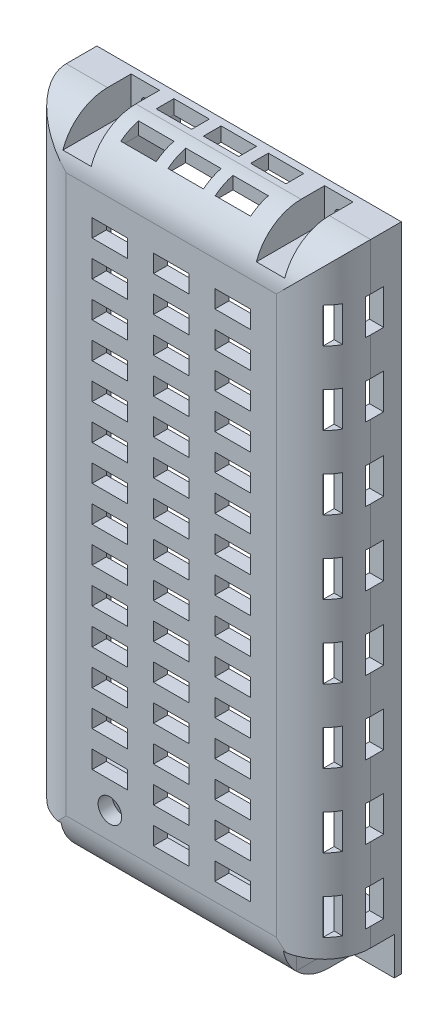
SolidWorks part; units mm, degrees
ref_plane "Plano frontal" through (0, 0, 0) normal (0, 0, 1) x (1, 0, 0)
ref_plane "Plano superior" through (0, 0, 0) normal (0, 1, 0) x (1, 0, 0)
ref_plane "Plano direito" through (0, 0, 0) normal (1, 0, 0) x (0, 0, -1)
sketch "Esboço1" plane through (0, 0, 0) normal (0, 0, 1) x (1, 0, 0)
  line L0 (-47.125, -132) -> (-47.125, -122)
  line L1 (-64.5, 138) -> (64.5, 138)
  line L2 (-64.5, 138) -> (-64.5, -138)
  line L3 (-64.5, -138) -> (64.5, -138)
  line L4 (64.5, 138) -> (64.5, -138)
  line L5 (0, -138) -> (0, 138) construction
  line L6 (-64.5, 0) -> (64.5, 0) construction
  line L7 (-58.5, 132) -> (58.5, 132) construction
  line L8 (-58.5, 132) -> (-58.5, -132) construction
  line L9 (-58.5, -132) -> (58.5, -132) construction
  line L10 (58.5, 132) -> (58.5, -132) construction
  line L11 (0, -132) -> (0, 132) construction
  line L12 (-58.5, 0) -> (58.5, 0) construction
  line L13 (-47.125, -122) -> (-58.5, -122)
  line L14 (-47, 132) -> (-47, 124.5)
  line L15 (-47, 124.5) -> (-35, 124.5)
  line L16 (-35, 124.5) -> (-35, 132)
  line L17 (-41, 130.5) -> (-41, 124.5) construction
  line L18 (-41, 130.5) -> (-35, 130.5) construction
  line L19 (-47, 132) -> (-58.5, 132)
  line L20 (-58.5, 132) -> (-58.5, -122)
  line L21 (41, 130.5) -> (35, 130.5) construction
  line L22 (41, 130.5) -> (41, 124.5) construction
  line L23 (47, 132) -> (58.5, 132)
  line L24 (35, 124.5) -> (35, 132)
  line L25 (47, 124.5) -> (35, 124.5)
  line L26 (47, 132) -> (47, 124.5)
  line L27 (58.5, 132) -> (58.5, -132) construction
  line L28 (58.5, 132) -> (58.5, -122)
  line L29 (47.125, -122) -> (58.5, -122)
  line L30 (47.125, -132) -> (47.125, -122)
  line L31 (-35, 132) -> (35, 132)
  line L32 (47.125, -132) -> (-47.125, -132)
  circle A0 centre (-53.125, -128) radius 1.6
  circle A1 centre (-41, 130.5) radius 1.6
  circle A2 centre (41, 130.5) radius 1.6
  circle A3 centre (53.125, -128) radius 1.6
  point P56 (0, 0)
  point P83 (0, 0)
  dimension "D5" = 3.2
  dimension "D8" = 3.2
  dimension "D1" = 129
  dimension "D2" = 276
  dimension "D3" = 6
  dimension "D4" = 6
  dimension "D6" = 11.375
  dimension "D7" = 10
  dimension "D9" = 23.5
  dimension "D10" = 7.5
  dimension "D11" = 6
  dimension "D12" = 6
  dimension "D13" = 6
extrude "Ressalto-extrusão1" add sketch "Esboço1" along normal blind 3
sketch "Esboço4" plane through (0, 0, 3) normal (0, 0, 1) x (1, 0, 0)
  line L0 (-64.5, 138) -> (-64.5, 72)
  line L1 (-64.5, 138) -> (-64.5, -138) construction
  line L2 (-64.5, 72) -> (-58.5, 72)
  line L3 (-58.5, 132) -> (-58.5, -122) construction
  line L4 (-58.5, 72) -> (-58.5, 132)
  line L5 (-58.5, 132) -> (-47, 132)
  line L6 (-47, 132) -> (-47, 138)
  line L7 (64.5, 138) -> (-64.5, 138) construction
  line L8 (-47, 138) -> (-64.5, 138)
  line L9 (-35, 132) -> (-35, 138)
  line L10 (-35, 138) -> (35, 138)
  line L11 (35, 138) -> (35, 132)
  line L12 (35, 132) -> (-35, 132)
  line L13 (47, 132) -> (47, 138)
  line L14 (47, 138) -> (64.5, 138)
  line L15 (64.5, 138) -> (64.5, 72)
  line L16 (64.5, -138) -> (64.5, 138) construction
  line L17 (64.5, 72) -> (58.5, 72)
  line L18 (58.5, -122) -> (58.5, 132) construction
  line L19 (58.5, 72) -> (58.5, 132)
  line L20 (58.5, 132) -> (47, 132)
  line L21 (-47.125, -132) -> (-47.125, -138)
  line L22 (-64.5, -138) -> (64.5, -138) construction
  line L23 (-47.125, -138) -> (47, -138)
  line L24 (47, -138) -> (47.125, -132)
  line L25 (47.125, -132) -> (-47.125, -132)
  line L26 (-58.5, -122) -> (-64.5, -122)
  line L27 (-64.5, -122) -> (-64.5, -22)
  line L28 (-64.5, -22) -> (-58.5, -22)
  line L29 (-58.5, -22) -> (-58.5, -122)
  line L30 (58.5, -122) -> (64.5, -122)
  line L31 (64.5, -122) -> (64.5, -22)
  line L32 (64.5, -22) -> (58.5, -22)
  line L33 (58.5, -22) -> (58.5, -122)
  dimension "D1" = 60
  dimension "D2" = 100
extrude "Ressalto-extrusão2" add sketch "Esboço4" along normal blind 24
sketch "Esboço5" plane through (0, 0, 27) normal (0, 0, 1) x (1, 0, 0)
  line L0 (-35, 132) -> (-35, 138)
  line L1 (-35, 138) -> (35, 138)
  line L2 (35, 138) -> (35, 132)
  line L3 (47, 132) -> (47, 138)
  line L4 (47, 138) -> (64.5, 138)
  line L5 (64.5, 138) -> (64.5, 72)
  line L6 (64.5, 72) -> (58.5, 72)
  line L7 (58.5, 72) -> (-64.5, 72)
  line L8 (-64.5, 72) -> (-64.5, 138)
  line L9 (-64.5, 138) -> (-47, 138)
  line L10 (-47, 138) -> (-47, 124.5)
  line L11 (-47, 124.5) -> (-35, 124.5)
  line L12 (-35, 124.5) -> (-35, 132)
  line L13 (35, 132) -> (35, 124.5)
  line L14 (35, 124.5) -> (47, 124.5)
  line L15 (47, 124.5) -> (47, 132)
  line L16 (-47.125, -138) -> (47, -138)
  line L17 (47, -138) -> (47.125, -122)
  line L18 (47.125, -122) -> (64.5, -122)
  line L19 (64.5, -122) -> (64.5, -22)
  line L20 (64.5, -22) -> (-64.5, -22)
  line L21 (-64.5, -22) -> (-64.5, -122)
  line L22 (-64.5, -122) -> (-47.125, -122)
  line L23 (-47.125, -122) -> (-47.125, -138)
extrude "Ressalto-extrusão3" add sketch "Esboço5" along normal blind 6
sketch "Esboço7" plane through (0, 0, 27) normal (0, 0, -1) x (-1, 0, 0)
  line L0 (-47, 132) -> (-53, 132)
  line L1 (-47, 132) -> (-58.5, 132) construction
  line L2 (-53, 132) -> (-53, 118.5)
  line L3 (-53, 118.5) -> (-29, 118.5)
  line L4 (-29, 118.5) -> (-29, 132)
  line L5 (35, 132) -> (-35, 132) construction
  line L6 (-29, 132) -> (-35, 132)
  line L7 (-35, 132) -> (-35, 124.5)
  line L8 (-35, 124.5) -> (-47, 124.5)
  line L9 (-47, 132) -> (-47, 124.5) construction
  line L10 (-47, 124.5) -> (-35, 124.5) construction
  line L11 (-47, 124.5) -> (-47, 132)
  line L19 (0, 0) -> (0, 50000) construction
  line L20 (58.5, -122) -> (58.5, -22) construction
  line L27 (47.125, -132) -> (47.125, -122)
  line L28 (47.125, -122) -> (58.5, -122)
  line L29 (58.5, -122) -> (58.5, -116)
  line L30 (58.5, -116) -> (41.125, -116)
  line L31 (41.125, -116) -> (41.125, -132)
  line L32 (-47.0469, -132) -> (47.125, -132) construction
  line L33 (41.125, -132) -> (47.125, -132)
  line L34 (47, 124.5) -> (47, 132)
  line L35 (35, 124.5) -> (47, 124.5)
  line L36 (35, 132) -> (35, 124.5)
  line L37 (29, 132) -> (35, 132)
  line L38 (29, 118.5) -> (29, 132)
  line L39 (53, 118.5) -> (29, 118.5)
  line L40 (53, 132) -> (53, 118.5)
  line L41 (47, 132) -> (53, 132)
  line L42 (-41.125, -132) -> (-47.125, -132)
  line L43 (-41.125, -116) -> (-41.125, -132)
  line L44 (-58.5, -116) -> (-41.125, -116)
  line L45 (-58.5, -122) -> (-58.5, -116)
  line L46 (-47.125, -122) -> (-58.5, -122)
  line L47 (-47.125, -132) -> (-47.125, -122)
  dimension "D1" = 6
  dimension "D2" = 6
  dimension "D5" = 6
extrude "Ressalto-extrusão5" add sketch "Esboço7" along normal up to vertex (27 mm away) up to point (35, 124.5, 0)
sketch "Esboço8" plane through (0, -22, 0) normal (0, 1, 0) x (1, 0, 0)
  line L0 (-58.5, -3) -> (-64.5, -3)
  line L1 (-64.5, -3) -> (-64.5, -33)
  line L2 (-64.5, -33) -> (64.5, -33)
  line L3 (64.5, -33) -> (64.5, -3)
  line L4 (64.5, -3) -> (58.5, -3)
  line L5 (58.5, -3) -> (58.5, -27)
  line L6 (58.5, -27) -> (-58.5, -27)
  line L7 (-58.5, -27) -> (-58.5, -3)
extrude "Ressalto-extrusão6" add sketch "Esboço8" along normal up to vertex (94 mm away) up to point (-58.5, 72, 27)
fillet "Filete1" radius 20 4 edges at (0, 138, 33) (-0.0625, -138, 33) (64.5, 8, 33) (-64.5, 8, 33)
sketch "Esboço9" plane through (0, 0, 33) normal (0, 0, 1) x (1, 0, 0)
  line L2 (-18.5, -106.75) -> (-7.5, -106.75) construction
  line L7 (-33.5, -103) -> (-18.5, -103) construction
  line L8 (-33.5, -103) -> (-33.5, -110.5) construction
  line L9 (-33.5, -110.5) -> (-18.5, -110.5) construction
  line L10 (-18.5, -103) -> (-18.5, -110.5) construction
  line L11 (-26, -110.5) -> (-26, -103) construction
  line L12 (-33.5, -106.75) -> (-18.5, -106.75) construction
  line L13 (-7.5, -103) -> (7.5, -103)
  line L14 (-7.5, -103) -> (-7.5, -110.5)
  line L15 (-7.5, -110.5) -> (7.5, -110.5)
  line L16 (7.5, -103) -> (7.5, -110.5)
  line L17 (0, -110.5) -> (0, -103) construction
  line L18 (-7.5, -106.75) -> (7.5, -106.75) construction
  line L19 (18.5, -103) -> (33.5, -103)
  line L20 (18.5, -103) -> (18.5, -110.5)
  line L21 (18.5, -110.5) -> (33.5, -110.5)
  line L22 (33.5, -103) -> (33.5, -110.5)
  line L23 (26, -110.5) -> (26, -103) construction
  line L24 (18.5, -106.75) -> (33.5, -106.75) construction
  line L25 (7.5, -106.75) -> (18.5, -106.75) construction
  line L26 (-33.5, -106.75) -> (-44.5, -106.75) construction
  line L27 (-44.5, 118) -> (-44.5, -118) construction
  line L28 (33.5, -106.75) -> (44.5, -106.75) construction
  line L29 (44.5, -118) -> (44.5, 118) construction
  line L30 (-44.5, -118) -> (44.5, -118) construction
  line L31 (-33.5, -88) -> (-18.5, -88)
  line L32 (-33.5, -88) -> (-33.5, -95.5)
  line L33 (-33.5, -95.5) -> (-18.5, -95.5)
  line L34 (-18.5, -88) -> (-18.5, -95.5)
  line L35 (-7.5, -88) -> (7.5, -88)
  line L36 (-7.5, -88) -> (-7.5, -95.5)
  line L37 (-7.5, -95.5) -> (7.5, -95.5)
  line L38 (7.5, -88) -> (7.5, -95.5)
  line L39 (18.5, -88) -> (33.5, -88)
  line L40 (18.5, -88) -> (18.5, -95.5)
  line L41 (18.5, -95.5) -> (33.5, -95.5)
  line L42 (33.5, -88) -> (33.5, -95.5)
  line L43 (-18.5, -91.75) -> (-7.5, -91.75) construction
  line L44 (-26, -95.5) -> (-26, -88) construction
  line L45 (-33.5, -91.75) -> (-18.5, -91.75) construction
  line L46 (0, -95.5) -> (0, -88) construction
  line L47 (-7.5, -91.75) -> (7.5, -91.75) construction
  line L48 (26, -95.5) -> (26, -88) construction
  line L49 (18.5, -91.75) -> (33.5, -91.75) construction
  line L50 (7.5, -91.75) -> (18.5, -91.75) construction
  line L51 (-33.5, -73) -> (-18.5, -73)
  line L52 (-33.5, -73) -> (-33.5, -80.5)
  line L53 (-33.5, -80.5) -> (-18.5, -80.5)
  line L54 (-18.5, -73) -> (-18.5, -80.5)
  line L55 (-7.5, -73) -> (7.5, -73)
  line L56 (-7.5, -73) -> (-7.5, -80.5)
  line L57 (-7.5, -80.5) -> (7.5, -80.5)
  line L58 (7.5, -73) -> (7.5, -80.5)
  line L59 (18.5, -73) -> (33.5, -73)
  line L60 (18.5, -73) -> (18.5, -80.5)
  line L61 (18.5, -80.5) -> (33.5, -80.5)
  line L62 (33.5, -73) -> (33.5, -80.5)
  line L63 (-18.5, -76.75) -> (-7.5, -76.75) construction
  line L64 (-26, -80.5) -> (-26, -73) construction
  line L65 (-33.5, -76.75) -> (-18.5, -76.75) construction
  line L66 (0, -80.5) -> (0, -73) construction
  line L67 (-7.5, -76.75) -> (7.5, -76.75) construction
  line L68 (26, -80.5) -> (26, -73) construction
  line L69 (18.5, -76.75) -> (33.5, -76.75) construction
  line L70 (7.5, -76.75) -> (18.5, -76.75) construction
  line L71 (-33.5, -58) -> (-18.5, -58)
  line L72 (-33.5, -58) -> (-33.5, -65.5)
  line L73 (-33.5, -65.5) -> (-18.5, -65.5)
  line L74 (-18.5, -58) -> (-18.5, -65.5)
  line L75 (-7.5, -58) -> (7.5, -58)
  line L76 (-7.5, -58) -> (-7.5, -65.5)
  line L77 (-7.5, -65.5) -> (7.5, -65.5)
  line L78 (7.5, -58) -> (7.5, -65.5)
  line L79 (18.5, -58) -> (33.5, -58)
  line L80 (18.5, -58) -> (18.5, -65.5)
  line L81 (18.5, -65.5) -> (33.5, -65.5)
  line L82 (33.5, -58) -> (33.5, -65.5)
  line L83 (-18.5, -61.75) -> (-7.5, -61.75) construction
  line L84 (-26, -65.5) -> (-26, -58) construction
  line L85 (-33.5, -61.75) -> (-18.5, -61.75) construction
  line L86 (0, -65.5) -> (0, -58) construction
  line L87 (-7.5, -61.75) -> (7.5, -61.75) construction
  line L88 (26, -65.5) -> (26, -58) construction
  line L89 (18.5, -61.75) -> (33.5, -61.75) construction
  line L90 (7.5, -61.75) -> (18.5, -61.75) construction
  line L91 (-33.5, -43) -> (-18.5, -43)
  line L92 (-33.5, -43) -> (-33.5, -50.5)
  line L93 (-33.5, -50.5) -> (-18.5, -50.5)
  line L94 (-18.5, -43) -> (-18.5, -50.5)
  line L95 (-7.5, -43) -> (7.5, -43)
  line L96 (-7.5, -43) -> (-7.5, -50.5)
  line L97 (-7.5, -50.5) -> (7.5, -50.5)
  line L98 (7.5, -43) -> (7.5, -50.5)
  line L99 (18.5, -43) -> (33.5, -43)
  line L100 (18.5, -43) -> (18.5, -50.5)
  line L101 (18.5, -50.5) -> (33.5, -50.5)
  line L102 (33.5, -43) -> (33.5, -50.5)
  line L103 (-18.5, -46.75) -> (-7.5, -46.75) construction
  line L104 (-26, -50.5) -> (-26, -43) construction
  line L105 (-33.5, -46.75) -> (-18.5, -46.75) construction
  line L106 (0, -50.5) -> (0, -43) construction
  line L107 (-7.5, -46.75) -> (7.5, -46.75) construction
  line L108 (26, -50.5) -> (26, -43) construction
  line L109 (18.5, -46.75) -> (33.5, -46.75) construction
  line L110 (7.5, -46.75) -> (18.5, -46.75) construction
  line L111 (-33.5, -28) -> (-18.5, -28)
  line L112 (-33.5, -28) -> (-33.5, -35.5)
  line L113 (-33.5, -35.5) -> (-18.5, -35.5)
  line L114 (-18.5, -28) -> (-18.5, -35.5)
  line L115 (-7.5, -28) -> (7.5, -28)
  line L116 (-7.5, -28) -> (-7.5, -35.5)
  line L117 (-7.5, -35.5) -> (7.5, -35.5)
  line L118 (7.5, -28) -> (7.5, -35.5)
  line L119 (18.5, -28) -> (33.5, -28)
  line L120 (18.5, -28) -> (18.5, -35.5)
  line L121 (18.5, -35.5) -> (33.5, -35.5)
  line L122 (33.5, -28) -> (33.5, -35.5)
  line L123 (-18.5, -31.75) -> (-7.5, -31.75) construction
  line L124 (-26, -35.5) -> (-26, -28) construction
  line L125 (-33.5, -31.75) -> (-18.5, -31.75) construction
  line L126 (0, -35.5) -> (0, -28) construction
  line L127 (-7.5, -31.75) -> (7.5, -31.75) construction
  line L128 (26, -35.5) -> (26, -28) construction
  line L129 (18.5, -31.75) -> (33.5, -31.75) construction
  line L130 (7.5, -31.75) -> (18.5, -31.75) construction
  line L131 (-33.5, -13) -> (-18.5, -13)
  line L132 (-33.5, -13) -> (-33.5, -20.5)
  line L133 (-33.5, -20.5) -> (-18.5, -20.5)
  line L134 (-18.5, -13) -> (-18.5, -20.5)
  line L135 (-7.5, -13) -> (7.5, -13)
  line L136 (-7.5, -13) -> (-7.5, -20.5)
  line L137 (-7.5, -20.5) -> (7.5, -20.5)
  line L138 (7.5, -13) -> (7.5, -20.5)
  line L139 (18.5, -13) -> (33.5, -13)
  line L140 (18.5, -13) -> (18.5, -20.5)
  line L141 (18.5, -20.5) -> (33.5, -20.5)
  line L142 (33.5, -13) -> (33.5, -20.5)
  line L143 (-18.5, -16.75) -> (-7.5, -16.75) construction
  line L144 (-26, -20.5) -> (-26, -13) construction
  line L145 (-33.5, -16.75) -> (-18.5, -16.75) construction
  line L146 (0, -20.5) -> (0, -13) construction
  line L147 (-7.5, -16.75) -> (7.5, -16.75) construction
  line L148 (26, -20.5) -> (26, -13) construction
  line L149 (18.5, -16.75) -> (33.5, -16.75) construction
  line L150 (7.5, -16.75) -> (18.5, -16.75) construction
  line L151 (-33.5, 2) -> (-18.5, 2)
  line L152 (-33.5, 2) -> (-33.5, -5.5)
  line L153 (-33.5, -5.5) -> (-18.5, -5.5)
  line L154 (-18.5, 2) -> (-18.5, -5.5)
  line L155 (-7.5, 2) -> (7.5, 2)
  line L156 (-7.5, 2) -> (-7.5, -5.5)
  line L157 (-7.5, -5.5) -> (7.5, -5.5)
  line L158 (7.5, 2) -> (7.5, -5.5)
  line L159 (18.5, 2) -> (33.5, 2)
  line L160 (18.5, 2) -> (18.5, -5.5)
  line L161 (18.5, -5.5) -> (33.5, -5.5)
  line L162 (33.5, 2) -> (33.5, -5.5)
  line L163 (-18.5, -1.75) -> (-7.5, -1.75) construction
  line L164 (-26, -5.5) -> (-26, 2) construction
  line L165 (-33.5, -1.75) -> (-18.5, -1.75) construction
  line L166 (0, -5.5) -> (0, 2) construction
  line L167 (-7.5, -1.75) -> (7.5, -1.75) construction
  line L168 (26, -5.5) -> (26, 2) construction
  line L169 (18.5, -1.75) -> (33.5, -1.75) construction
  line L170 (7.5, -1.75) -> (18.5, -1.75) construction
  line L171 (-33.5, 17) -> (-18.5, 17)
  line L172 (-33.5, 17) -> (-33.5, 9.5)
  line L173 (-33.5, 9.5) -> (-18.5, 9.5)
  line L174 (-18.5, 17) -> (-18.5, 9.5)
  line L175 (-7.5, 17) -> (7.5, 17)
  line L176 (-7.5, 17) -> (-7.5, 9.5)
  line L177 (-7.5, 9.5) -> (7.5, 9.5)
  line L178 (7.5, 17) -> (7.5, 9.5)
  line L179 (18.5, 17) -> (33.5, 17)
  line L180 (18.5, 17) -> (18.5, 9.5)
  line L181 (18.5, 9.5) -> (33.5, 9.5)
  line L182 (33.5, 17) -> (33.5, 9.5)
  line L183 (-18.5, 13.25) -> (-7.5, 13.25) construction
  line L184 (-26, 9.5) -> (-26, 17) construction
  line L185 (-33.5, 13.25) -> (-18.5, 13.25) construction
  line L186 (0, 9.5) -> (0, 17) construction
  line L187 (-7.5, 13.25) -> (7.5, 13.25) construction
  line L188 (26, 9.5) -> (26, 17) construction
  line L189 (18.5, 13.25) -> (33.5, 13.25) construction
  line L190 (7.5, 13.25) -> (18.5, 13.25) construction
  line L191 (-33.5, 32) -> (-18.5, 32)
  line L192 (-33.5, 32) -> (-33.5, 24.5)
  line L193 (-33.5, 24.5) -> (-18.5, 24.5)
  line L194 (-18.5, 32) -> (-18.5, 24.5)
  line L195 (-7.5, 32) -> (7.5, 32)
  line L196 (-7.5, 32) -> (-7.5, 24.5)
  line L197 (-7.5, 24.5) -> (7.5, 24.5)
  line L198 (7.5, 32) -> (7.5, 24.5)
  line L199 (18.5, 32) -> (33.5, 32)
  line L200 (18.5, 32) -> (18.5, 24.5)
  line L201 (18.5, 24.5) -> (33.5, 24.5)
  line L202 (33.5, 32) -> (33.5, 24.5)
  line L203 (-18.5, 28.25) -> (-7.5, 28.25) construction
  line L204 (-26, 24.5) -> (-26, 32) construction
  line L205 (-33.5, 28.25) -> (-18.5, 28.25) construction
  line L206 (0, 24.5) -> (0, 32) construction
  line L207 (-7.5, 28.25) -> (7.5, 28.25) construction
  line L208 (26, 24.5) -> (26, 32) construction
  line L209 (18.5, 28.25) -> (33.5, 28.25) construction
  line L210 (7.5, 28.25) -> (18.5, 28.25) construction
  line L211 (-33.5, 47) -> (-18.5, 47)
  line L212 (-33.5, 47) -> (-33.5, 39.5)
  line L213 (-33.5, 39.5) -> (-18.5, 39.5)
  line L214 (-18.5, 47) -> (-18.5, 39.5)
  line L215 (-7.5, 47) -> (7.5, 47)
  line L216 (-7.5, 47) -> (-7.5, 39.5)
  line L217 (-7.5, 39.5) -> (7.5, 39.5)
  line L218 (7.5, 47) -> (7.5, 39.5)
  line L219 (18.5, 47) -> (33.5, 47)
  line L220 (18.5, 47) -> (18.5, 39.5)
  line L221 (18.5, 39.5) -> (33.5, 39.5)
  line L222 (33.5, 47) -> (33.5, 39.5)
  line L223 (-18.5, 43.25) -> (-7.5, 43.25) construction
  line L224 (-26, 39.5) -> (-26, 47) construction
  line L225 (-33.5, 43.25) -> (-18.5, 43.25) construction
  line L226 (0, 39.5) -> (0, 47) construction
  line L227 (-7.5, 43.25) -> (7.5, 43.25) construction
  line L228 (26, 39.5) -> (26, 47) construction
  line L229 (18.5, 43.25) -> (33.5, 43.25) construction
  line L230 (7.5, 43.25) -> (18.5, 43.25) construction
  line L231 (-33.5, 62) -> (-18.5, 62)
  line L232 (-33.5, 62) -> (-33.5, 54.5)
  line L233 (-33.5, 54.5) -> (-18.5, 54.5)
  line L234 (-18.5, 62) -> (-18.5, 54.5)
  line L235 (-7.5, 62) -> (7.5, 62)
  line L236 (-7.5, 62) -> (-7.5, 54.5)
  line L237 (-7.5, 54.5) -> (7.5, 54.5)
  line L238 (7.5, 62) -> (7.5, 54.5)
  line L239 (18.5, 62) -> (33.5, 62)
  line L240 (18.5, 62) -> (18.5, 54.5)
  line L241 (18.5, 54.5) -> (33.5, 54.5)
  line L242 (33.5, 62) -> (33.5, 54.5)
  line L243 (-18.5, 58.25) -> (-7.5, 58.25) construction
  line L244 (-26, 54.5) -> (-26, 62) construction
  line L245 (-33.5, 58.25) -> (-18.5, 58.25) construction
  line L246 (0, 54.5) -> (0, 62) construction
  line L247 (-7.5, 58.25) -> (7.5, 58.25) construction
  line L248 (26, 54.5) -> (26, 62) construction
  line L249 (18.5, 58.25) -> (33.5, 58.25) construction
  line L250 (7.5, 58.25) -> (18.5, 58.25) construction
  line L251 (-33.5, 77) -> (-18.5, 77)
  line L252 (-33.5, 77) -> (-33.5, 69.5)
  line L253 (-33.5, 69.5) -> (-18.5, 69.5)
  line L254 (-18.5, 77) -> (-18.5, 69.5)
  line L255 (-7.5, 77) -> (7.5, 77)
  line L256 (-7.5, 77) -> (-7.5, 69.5)
  line L257 (-7.5, 69.5) -> (7.5, 69.5)
  line L258 (7.5, 77) -> (7.5, 69.5)
  line L259 (18.5, 77) -> (33.5, 77)
  line L260 (18.5, 77) -> (18.5, 69.5)
  line L261 (18.5, 69.5) -> (33.5, 69.5)
  line L262 (33.5, 77) -> (33.5, 69.5)
  line L263 (-18.5, 73.25) -> (-7.5, 73.25) construction
  line L264 (-26, 69.5) -> (-26, 77) construction
  line L265 (-33.5, 73.25) -> (-18.5, 73.25) construction
  line L266 (0, 69.5) -> (0, 77) construction
  line L267 (-7.5, 73.25) -> (7.5, 73.25) construction
  line L268 (26, 69.5) -> (26, 77) construction
  line L269 (18.5, 73.25) -> (33.5, 73.25) construction
  line L270 (7.5, 73.25) -> (18.5, 73.25) construction
  line L271 (-33.5, 92) -> (-18.5, 92)
  line L272 (-33.5, 92) -> (-33.5, 84.5)
  line L273 (-33.5, 84.5) -> (-18.5, 84.5)
  line L274 (-18.5, 92) -> (-18.5, 84.5)
  line L275 (-7.5, 92) -> (7.5, 92)
  line L276 (-7.5, 92) -> (-7.5, 84.5)
  line L277 (-7.5, 84.5) -> (7.5, 84.5)
  line L278 (7.5, 92) -> (7.5, 84.5)
  line L279 (18.5, 92) -> (33.5, 92)
  line L280 (18.5, 92) -> (18.5, 84.5)
  line L281 (18.5, 84.5) -> (33.5, 84.5)
  line L282 (33.5, 92) -> (33.5, 84.5)
  line L283 (-18.5, 88.25) -> (-7.5, 88.25) construction
  line L284 (-26, 84.5) -> (-26, 92) construction
  line L285 (-33.5, 88.25) -> (-18.5, 88.25) construction
  line L286 (0, 84.5) -> (0, 92) construction
  line L287 (-7.5, 88.25) -> (7.5, 88.25) construction
  line L288 (26, 84.5) -> (26, 92) construction
  line L289 (18.5, 88.25) -> (33.5, 88.25) construction
  line L290 (7.5, 88.25) -> (18.5, 88.25) construction
  line L291 (-33.5, 107) -> (-18.5, 107)
  line L292 (-33.5, 107) -> (-33.5, 99.5)
  line L293 (-33.5, 99.5) -> (-18.5, 99.5)
  line L294 (-18.5, 107) -> (-18.5, 99.5)
  line L295 (-7.5, 107) -> (7.5, 107)
  line L296 (-7.5, 107) -> (-7.5, 99.5)
  line L297 (-7.5, 99.5) -> (7.5, 99.5)
  line L298 (7.5, 107) -> (7.5, 99.5)
  line L299 (18.5, 107) -> (33.5, 107)
  line L300 (18.5, 107) -> (18.5, 99.5)
  line L301 (18.5, 99.5) -> (33.5, 99.5)
  line L302 (33.5, 107) -> (33.5, 99.5)
  line L303 (-18.5, 103.25) -> (-7.5, 103.25) construction
  line L304 (-26, 99.5) -> (-26, 107) construction
  line L305 (-33.5, 103.25) -> (-18.5, 103.25) construction
  line L306 (0, 99.5) -> (0, 107) construction
  line L307 (-7.5, 103.25) -> (7.5, 103.25) construction
  line L308 (26, 99.5) -> (26, 107) construction
  line L309 (18.5, 103.25) -> (33.5, 103.25) construction
  line L310 (7.5, 103.25) -> (18.5, 103.25) construction
  circle A1 centre (-26, -106.75) radius 5
  point P38 (0, -91.75)
  point P43 (26, -91.75)
  point P48 (-26, -91.75)
  point P65 (0, -76.75)
  point P70 (26, -76.75)
  point P75 (-26, -76.75)
  point P92 (0, -61.75)
  point P97 (26, -61.75)
  point P102 (-26, -61.75)
  point P112 (0, -106.75)
  point P123 (0, -46.75)
  point P128 (26, -46.75)
  point P133 (-26, -46.75)
  point P145 (26, -106.75)
  point P155 (0, -31.75)
  point P160 (26, -31.75)
  point P165 (-26, -31.75)
  point P180 (-26, -106.75)
  point P187 (0, -16.75)
  point P192 (26, -16.75)
  point P197 (-26, -16.75)
  point P214 (0, -1.75)
  point P219 (26, -1.75)
  point P224 (-26, -1.75)
  point P241 (0, 13.25)
  point P246 (26, 13.25)
  point P251 (-26, 13.25)
  point P268 (0, 28.25)
  point P273 (26, 28.25)
  point P278 (-26, 28.25)
  point P295 (0, 43.25)
  point P300 (26, 43.25)
  point P305 (-26, 43.25)
  point P322 (0, 58.25)
  point P327 (26, 58.25)
  point P332 (-26, 58.25)
  point P349 (0, 73.25)
  point P354 (26, 73.25)
  point P359 (-26, 73.25)
  point P376 (0, 88.25)
  point P381 (26, 88.25)
  point P386 (-26, 88.25)
  point P403 (0, 103.25)
  point P408 (26, 103.25)
  point P413 (-26, 103.25)
  dimension "D1" = 15
  dimension "D5" = 10
  dimension "D2" = 7.5
  dimension "D3" = 7.5
  dimension "D4" = 15
extrude "Corte-extrusão1" cut sketch "Esboço9" against normal up to next (6 mm away)
sketch "Esboço10" plane through (0, -138, 0) normal (0, -1, 0) x (1, 0, 0)
  line L0 (47, 13) -> (-47.125, 13) construction
  line L1 (-39.625, 28) -> (-24.625, 28)
  line L2 (-39.625, 28) -> (-39.625, 20.5)
  line L3 (-39.625, 20.5) -> (-24.625, 20.5)
  line L4 (-24.625, 28) -> (-24.625, 20.5)
  line L5 (-32.125, 20.5) -> (-32.125, 28) construction
  line L6 (-39.625, 24.25) -> (-24.625, 24.25) construction
  line L7 (-47.125, 32.5959) -> (-47.125, 13) construction
  line L8 (-9.625, 28) -> (5.375, 28)
  line L9 (-9.625, 28) -> (-9.625, 20.5)
  line L10 (-9.625, 20.5) -> (5.375, 20.5)
  line L11 (5.375, 28) -> (5.375, 20.5)
  line L12 (-2.125, 20.5) -> (-2.125, 28) construction
  line L13 (-9.625, 24.25) -> (5.375, 24.25) construction
  line L14 (20.375, 28) -> (35.375, 28)
  line L15 (20.375, 28) -> (20.375, 20.5)
  line L16 (20.375, 20.5) -> (35.375, 20.5)
  line L17 (35.375, 28) -> (35.375, 20.5)
  line L18 (27.875, 20.5) -> (27.875, 28) construction
  line L19 (20.375, 24.25) -> (35.375, 24.25) construction
  line L20 (-39.625, 15.5) -> (-24.625, 15.5)
  line L21 (-39.625, 15.5) -> (-39.625, 8)
  line L22 (-39.625, 8) -> (-24.625, 8)
  line L23 (-24.625, 15.5) -> (-24.625, 8)
  line L24 (-9.625, 15.5) -> (5.375, 15.5)
  line L25 (-9.625, 15.5) -> (-9.625, 8)
  line L26 (-9.625, 8) -> (5.375, 8)
  line L27 (5.375, 15.5) -> (5.375, 8)
  line L28 (20.375, 15.5) -> (35.375, 15.5)
  line L29 (20.375, 15.5) -> (20.375, 8)
  line L30 (20.375, 8) -> (35.375, 8)
  line L31 (35.375, 15.5) -> (35.375, 8)
  line L32 (-32.125, 8) -> (-32.125, 15.5) construction
  line L33 (-39.625, 11.75) -> (-24.625, 11.75) construction
  line L34 (-2.125, 8) -> (-2.125, 15.5) construction
  line L35 (-9.625, 11.75) -> (5.375, 11.75) construction
  line L36 (27.875, 8) -> (27.875, 15.5) construction
  line L37 (20.375, 11.75) -> (35.375, 11.75) construction
  point P17 (-2.125, 24.25)
  point P26 (27.875, 24.25)
  point P39 (-2.125, 11.75)
  point P48 (27.875, 11.75)
  point P53 (-32.125, 11.75)
  point P132 (-32.125, 24.25)
  dimension "D1" = 15
  dimension "D2" = 7.5
  dimension "D3" = 7.5
  dimension "D4" = 7.5
  dimension "D5" = 3
  dimension "D6" = 2
extrude "Corte-extrusão2" cut sketch "Esboço10" against normal up to vertex (6 mm away) up to point (41.125, -132, 27)
sketch "Esboço11" plane through (0, 138, 0) normal (0, 1, 0) x (1, 0, 0)
  line L0 (44.5, -33) -> (-44.5, -33) construction
  line L1 (-28.8651, -18) -> (-13.8651, -18)
  line L2 (-28.8651, -18) -> (-28.8651, -25.5)
  line L3 (-28.8651, -25.5) -> (-13.8651, -25.5)
  line L4 (-13.8651, -18) -> (-13.8651, -25.5)
  line L5 (-21.3651, -25.5) -> (-21.3651, -18) construction
  line L6 (-28.8651, -21.75) -> (-13.8651, -21.75) construction
  line L7 (-8.8651, -18) -> (6.1349, -18)
  line L8 (-8.8651, -18) -> (-8.8651, -25.5)
  line L9 (-8.8651, -25.5) -> (6.1349, -25.5)
  line L10 (6.1349, -18) -> (6.1349, -25.5)
  line L11 (-1.3651, -25.5) -> (-1.3651, -18) construction
  line L12 (-8.8651, -21.75) -> (6.1349, -21.75) construction
  line L13 (11.1349, -18) -> (26.1349, -18)
  line L14 (11.1349, -18) -> (11.1349, -25.5)
  line L15 (11.1349, -25.5) -> (26.1349, -25.5)
  line L16 (26.1349, -18) -> (26.1349, -25.5)
  line L17 (18.6349, -25.5) -> (18.6349, -18) construction
  line L18 (11.1349, -21.75) -> (26.1349, -21.75) construction
  line L19 (-8.8651, -3) -> (6.1349, -3)
  line L20 (-8.8651, -3) -> (-8.8651, -10.5)
  line L21 (-8.8651, -10.5) -> (6.1349, -10.5)
  line L22 (6.1349, -3) -> (6.1349, -10.5)
  line L23 (-1.3651, -10.5) -> (-1.3651, -3) construction
  line L24 (-8.8651, -6.75) -> (6.1349, -6.75) construction
  line L25 (11.1349, -3) -> (26.1349, -3)
  line L26 (11.1349, -3) -> (11.1349, -10.5)
  line L27 (11.1349, -10.5) -> (26.1349, -10.5)
  line L28 (26.1349, -3) -> (26.1349, -10.5)
  line L29 (18.6349, -10.5) -> (18.6349, -3) construction
  line L30 (11.1349, -6.75) -> (26.1349, -6.75) construction
  line L31 (-28.8651, -3) -> (-13.8651, -3)
  line L32 (-28.8651, -3) -> (-28.8651, -10.5)
  line L33 (-28.8651, -10.5) -> (-13.8651, -10.5)
  line L34 (-13.8651, -3) -> (-13.8651, -10.5)
  line L35 (-21.3651, -10.5) -> (-21.3651, -3) construction
  line L36 (-28.8651, -6.75) -> (-13.8651, -6.75) construction
  point P16 (-1.3651, -21.75)
  point P28 (-21.3651, -21.75)
  point P30 (18.6349, -21.75)
  point P39 (-1.3651, -6.75)
  point P48 (18.6349, -6.75)
  point P57 (-21.3651, -6.75)
  dimension "D1" = 7.5
  dimension "D2" = 15
  dimension "D3" = 7.5
  dimension "D4" = 3
  dimension "D5" = 2
extrude "Corte-extrusão3" cut sketch "Esboço11" against normal up to vertex (6 mm away) up to point (-29, 132, 27)
sketch "Esboço12" plane through (-64.5, 0, 0) normal (-1, 0, 0) x (0, 0, 1)
  line L0 (15, 118) -> (33, 118) construction
  line L1 (7.5, 118) -> (15, 118)
  line L2 (7.5, 118) -> (7.5, 103)
  line L3 (7.5, 103) -> (15, 103)
  line L4 (15, 118) -> (15, 103)
  line L5 (11.25, 103) -> (11.25, 118) construction
  line L6 (7.5, 110.5) -> (15, 110.5) construction
  line L7 (0, 138) -> (0, -138) construction
  line L8 (22.5, 118) -> (30, 118)
  line L9 (22.5, 118) -> (22.5, 103)
  line L10 (22.5, 103) -> (30, 103)
  line L11 (30, 118) -> (30, 103)
  line L12 (26.25, 103) -> (26.25, 118) construction
  line L13 (22.5, 110.5) -> (30, 110.5) construction
  line L14 (22.5, 87) -> (30, 87)
  line L15 (22.5, 87) -> (22.5, 72)
  line L16 (22.5, 72) -> (30, 72)
  line L17 (30, 87) -> (30, 72)
  line L18 (26.25, 72) -> (26.25, 87) construction
  line L19 (22.5, 79.5) -> (30, 79.5) construction
  line L20 (22.5, 56) -> (30, 56)
  line L21 (22.5, 56) -> (22.5, 41)
  line L22 (22.5, 41) -> (30, 41)
  line L23 (30, 56) -> (30, 41)
  line L24 (26.25, 41) -> (26.25, 56) construction
  line L25 (22.5, 48.5) -> (30, 48.5) construction
  line L26 (22.5, 25) -> (30, 25)
  line L27 (22.5, 25) -> (22.5, 10)
  line L28 (22.5, 10) -> (30, 10)
  line L29 (30, 25) -> (30, 10)
  line L30 (26.25, 10) -> (26.25, 25) construction
  line L31 (22.5, 17.5) -> (30, 17.5) construction
  line L32 (22.5, -6) -> (30, -6)
  line L33 (22.5, -6) -> (22.5, -21)
  line L34 (22.5, -21) -> (30, -21)
  line L35 (30, -6) -> (30, -21)
  line L36 (26.25, -21) -> (26.25, -6) construction
  line L37 (22.5, -13.5) -> (30, -13.5) construction
  line L38 (22.5, -37) -> (30, -37)
  line L39 (22.5, -37) -> (22.5, -52)
  line L40 (22.5, -52) -> (30, -52)
  line L41 (30, -37) -> (30, -52)
  line L42 (26.25, -52) -> (26.25, -37) construction
  line L43 (22.5, -44.5) -> (30, -44.5) construction
  line L44 (22.5, -68) -> (30, -68)
  line L45 (22.5, -68) -> (22.5, -83)
  line L46 (22.5, -83) -> (30, -83)
  line L47 (30, -68) -> (30, -83)
  line L48 (26.25, -83) -> (26.25, -68) construction
  line L49 (22.5, -75.5) -> (30, -75.5) construction
  line L50 (22.5, -99) -> (30, -99)
  line L51 (22.5, -99) -> (22.5, -114)
  line L52 (22.5, -114) -> (30, -114)
  line L53 (30, -99) -> (30, -114)
  line L54 (26.25, -114) -> (26.25, -99) construction
  line L55 (22.5, -106.5) -> (30, -106.5) construction
  line L56 (7.5, 87) -> (15, 87)
  line L57 (7.5, 87) -> (7.5, 72)
  line L58 (7.5, 72) -> (15, 72)
  line L59 (15, 87) -> (15, 72)
  line L60 (11.25, 72) -> (11.25, 87) construction
  line L61 (7.5, 79.5) -> (15, 79.5) construction
  line L62 (7.5, 56) -> (15, 56)
  line L63 (7.5, 56) -> (7.5, 41)
  line L64 (7.5, 41) -> (15, 41)
  line L65 (15, 56) -> (15, 41)
  line L66 (11.25, 41) -> (11.25, 56) construction
  line L67 (7.5, 48.5) -> (15, 48.5) construction
  line L68 (7.5, 25) -> (15, 25)
  line L69 (7.5, 25) -> (7.5, 10)
  line L70 (7.5, 10) -> (15, 10)
  line L71 (15, 25) -> (15, 10)
  line L72 (11.25, 10) -> (11.25, 25) construction
  line L73 (7.5, 17.5) -> (15, 17.5) construction
  line L74 (7.5, -6) -> (15, -6)
  line L75 (7.5, -6) -> (7.5, -21)
  line L76 (7.5, -21) -> (15, -21)
  line L77 (15, -6) -> (15, -21)
  line L78 (11.25, -21) -> (11.25, -6) construction
  line L79 (7.5, -13.5) -> (15, -13.5) construction
  line L80 (7.5, -37) -> (15, -37)
  line L81 (7.5, -37) -> (7.5, -52)
  line L82 (7.5, -52) -> (15, -52)
  line L83 (15, -37) -> (15, -52)
  line L84 (11.25, -52) -> (11.25, -37) construction
  line L85 (7.5, -44.5) -> (15, -44.5) construction
  line L86 (7.5, -68) -> (15, -68)
  line L87 (7.5, -68) -> (7.5, -83)
  line L88 (7.5, -83) -> (15, -83)
  line L89 (15, -68) -> (15, -83)
  line L90 (11.25, -83) -> (11.25, -68) construction
  line L91 (7.5, -75.5) -> (15, -75.5) construction
  line L92 (7.5, -99) -> (15, -99)
  line L93 (7.5, -99) -> (7.5, -114)
  line L94 (7.5, -114) -> (15, -114)
  line L95 (15, -99) -> (15, -114)
  line L96 (11.25, -114) -> (11.25, -99) construction
  line L97 (7.5, -106.5) -> (15, -106.5) construction
  point P17 (26.25, 110.5)
  point P26 (26.25, 79.5)
  point P35 (26.25, 48.5)
  point P44 (26.25, 17.5)
  point P53 (26.25, -13.5)
  point P62 (26.25, -44.5)
  point P71 (26.25, -75.5)
  point P80 (26.25, -106.5)
  point P89 (11.25, 79.5)
  point P100 (11.25, 110.5)
  point P104 (11.25, 48.5)
  point P113 (11.25, 17.5)
  point P122 (11.25, -13.5)
  point P131 (11.25, -44.5)
  point P140 (11.25, -75.5)
  point P149 (11.25, -106.5)
  dimension "D1" = 15
  dimension "D2" = 7.5
  dimension "D3" = 7.5
  dimension "D4" = 2
  dimension "D5" = 8
extrude "Corte-extrusão4" cut sketch "Esboço12" against normal up to vertex (6 mm away) up to point (-58.5, -116, 27)
mirror "Espelhar2" about plane through (0, 0, 0) normal (1, 0, 0) of "Corte-extrusão4"
